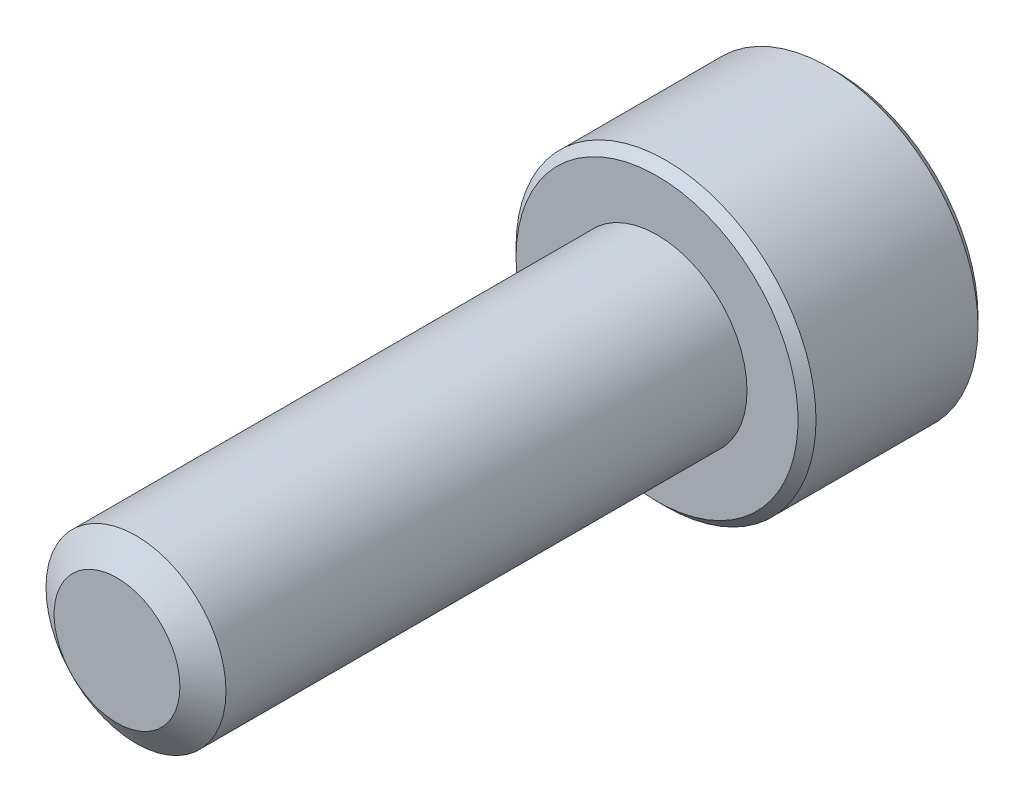
SolidWorks part; units mm, degrees
material "Alloy Steel"
ref_plane "Front Plane" through (0, 0, 0) normal (0, 0, 1) x (1, 0, 0)
ref_plane "Top Plane" through (0, 0, 0) normal (0, 1, 0) x (1, 0, 0)
ref_plane "Right Plane" through (0, 0, 0) normal (1, 0, 0) x (0, 0, -1)
sketch "Sketch1" plane through (0, 0, 0) normal (0, 0, 1) x (1, 0, 0)
  circle A0 centre (0, 0) radius 3
  dimension "OD" = 6
extrude "Extrude1" add sketch "Sketch1" against normal blind 18
sketch "Sketch2" plane through (0, 0, 0) normal (0, 0, 1) x (1, 0, 0)
  circle A0 centre (0, 0) radius 3 construction
  circle A1 centre (0, 0) radius 3
curve "Helix/Spiral1" pitch 1 height 19 turns 19 parameters "pitch"=1
sketch "Sketch3" plane through (0, 0, 0) normal (1, 0, 0) x (0, 0, -1)
  line L0 (-0.875, 3) -> (-0.5, 2.3505)
  line L1 (-0.5, 2.3505) -> (-0.375, 2.3505)
  line L2 (-0.375, 2.3505) -> (0, 3)
  line L3 (-0.875, 3) -> (0, 3)
  line L4 (-0.4375, 3) -> (-0.4375, 2.3505) construction
  line L5 (-0.6875, 2.6752) -> (-0.1875, 2.6752) construction
  line L6 (0, 3) -> (0, -3) construction
  line L7 (0, -3) -> (18, -3) construction
  point P11 (4.5, -3)
  dimension "D1" = 0.125
  dimension "D2" = 0.5
  dimension "D3" = 60
  dimension "D4" = 4.5
sweep "Cut-Sweep1" [suppressed] cut profiles "Sketch3" path "Helix/Spiral1"
sketch "Sketch4" plane through (0, 0, 0) normal (1, 0, 0) x (0, 0, -1)
  line L0 (0.6327, 3) -> (0, 2.0965)
  line L1 (0, 2.0965) -> (0, 3)
  line L2 (0.6327, 3) -> (0, 3)
  line L3 (-0.875, 3) -> (0, 3) construction
  line L4 (0, 0) -> (7.0209, 0) construction
  dimension "D1" = 55
  dimension "D2" = 0.254
revolve "Cut-Revolve1" cut sketch "Sketch4" angle 360 about L4
sketch "Sketch5" [suppressed] plane through (0, 0, 0) normal (1, 0, 0) x (0, 0, -1)
  line L0 (18, -2.3644) -> (18, 2.1406) construction
  line L1 (18, 3) -> (0.1203, 3)
  line L2 (18, 3) -> (18, 0)
  line L3 (18, 0) -> (0.0001, 0)
  line L4 (0.0001, 2.6698) -> (0.0001, 0)
  line L5 (0.1203, 3) -> (0.0001, 2.6698)
  line L6 (0, 0) -> (9.9695, 0) construction
  point P3 (0.0001, 3)
  point P10 (0.0001, 3)
  dimension "D1" = 0.3302
  dimension "Thread min" = 0.0001
  dimension "D3" = 20
revolve "partially thread" [suppressed] add sketch "Sketch5" angle 360 about L6
sketch "Sketch6" plane through (0, 0, -18) normal (0, 0, -1) x (-1, 0, 0)
  circle A0 centre (0, 0) radius 5
  dimension "head dia" = 10
extrude "Extrude2" add sketch "Sketch6" along normal blind 6
sketch "Sketch7" plane through (0, 0, -24) normal (0, 0, -1) x (-1, 0, 0)
  line L1 (0, 2.8868) -> (-2.5, 1.4434)
  line L2 (-2.5, 1.4434) -> (-2.5, -1.4434)
  line L3 (-2.5, -1.4434) -> (0, -2.8868)
  line L4 (0, -2.8868) -> (2.5, -1.4434)
  line L5 (2.5, -1.4434) -> (2.5, 1.4434)
  line L6 (2.5, 1.4434) -> (0, 2.8868)
  circle A0 centre (0, 0) radius 2.5 construction
  dimension "hex dia" = 5
extrude "Cut-Extrude1" cut sketch "Sketch7" against normal blind 3.75
sketch "Sketch8" plane through (0, 0, -24) normal (0, 0, -1) x (-1, 0, 0)
  circle A0 centre (0, 0) radius 2.8868
extrude "Cut-Extrude2" cut sketch "Sketch8" against normal through all draft 45
chamfer "Chamfer1" distance 0.3 angle 45 2 edges at (-5, 0, -24) (-5, 0, -18)
sketch "Sketch9" plane through (0, 0, 0) normal (1, 0, 0) x (0, 0, -1)
  line L0 (0, 3) -> (0, -3) construction
  line L1 (5.5, 3) -> (5.5, -3) construction
  dimension "D1" = 5.5
sketch "Sketch10" plane through (0, 0, 0) normal (1, 0, 0) x (0, 0, -1)
  line L0 (18, 3) -> (18, 0)
  line L1 (18, 3) -> (17.75, 3)
  line L2 (17.75, 3) -> (16.5074, 0)
  line L3 (18, 0) -> (16.5074, 0)
  line L4 (18, 4.7) -> (18, -4.7) construction
  dimension "D1" = 22.5
  dimension "D2" = 0.25
revolve "Revolve1" add sketch "Sketch10" angle 360 about L3
equation "\"D3@Helix/Spiral1\" = \"screw length@Extrude1\"+\"pitch@Helix/Spiral1\""
equation "\"D1@Sketch3\" = \"pitch@Helix/Spiral1\"*.125"
equation "\"D2@Sketch3\" = \"pitch@Helix/Spiral1\"*.5"
equation "\"D1@Cut-Extrude1\" = \"hex dia@Sketch7\"*.75"
equation "\"D1@Chamfer1\" = \"head dia@Sketch6\"*.03"
equation "\"D1@Sketch9\" = \"pitch@Helix/Spiral1\"*5.5"
equation "\"D2@Sketch10\" = \"pitch@Helix/Spiral1\"*.25"
equation "\"D4@Sketch3\" = \"pitch@Helix/Spiral1\"*4.50"
